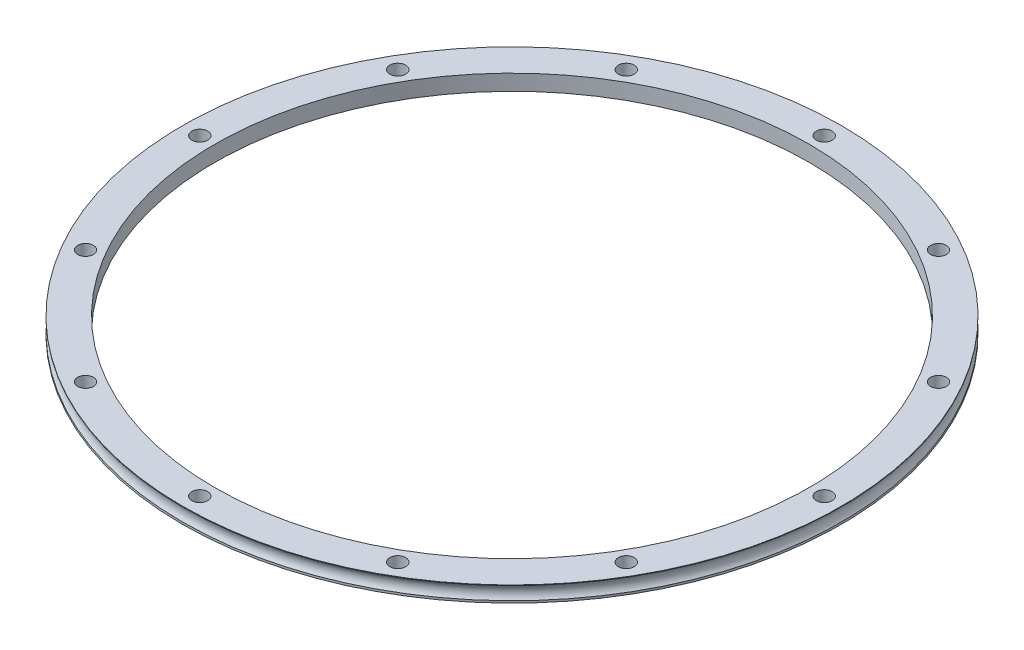
SolidWorks part; units mm, degrees
material "AISI 4340 Steel, normalized"
ref_plane "Front Plane" through (0, 0, 0) normal (0, 0, 1) x (1, 0, 0)
ref_plane "Top Plane" through (0, 0, 0) normal (0, 1, 0) x (1, 0, 0)
ref_plane "Right Plane" through (0, 0, 0) normal (1, 0, 0) x (0, 0, -1)
sketch "Sketch1" plane through (0, 0, 0) normal (0, 0, 1) x (1, 0, 0)
  line L1 (-60, 6.785) -> (-60, 9.965) construction
  line L2 (-60, 6.785) -> (-66.5, 6.785) construction
  line L3 (-66.5, 6.785) -> (-66.5, 7.2121) construction
  line L4 (-66.5, 9.8579) -> (-66.5, 9.965)
  line L5 (-60, 6.785) -> (-60, 9.965)
  line L6 (-60, 6.785) -> (-66.5, 6.785)
  line L7 (-66.5, 6.785) -> (-66.5, 7.2121)
  line L8 (-60, 9.965) -> (-66.5, 9.965)
  line L10 (0, -200069.0475) -> (0, 200086.9028) construction
  line L11 (0, -200069.0475) -> (0, 200086.9028) construction
  arc A0 (-66.5, 7.2121) -> (-66.5, 9.8579) centre (-68, 8.535) ccw construction
  arc A1 (-66.5, 7.2121) -> (-66.5, 9.8579) centre (-68, 8.535) ccw
revolve "Revolve1" add sketch "Sketch1" angle 360 about L11
ref_plane "Midplane" through (0, 8.375, 0) normal (0, 1, 0) x (1, 0, 0)
split "Split1" [suppressed] bodies to split 101
sketch "Sketch3" plane through (0, 9.965, 0) normal (0, 1, 0) x (1, 0, 0)
  circle A1 centre (0, 63) radius 1.6
  circle A2 centre (0, 63) radius 1.6
  dimension "D1" = 0
extrude "Cut-Extrude1" cut sketch "Sketch3" against normal through all
pattern_circular "CirPattern1" count 12 over 360 about axis through (0, -200069.0475, 0) along (0, -1, 0) of "Cut-Extrude1" reverse direction yes
